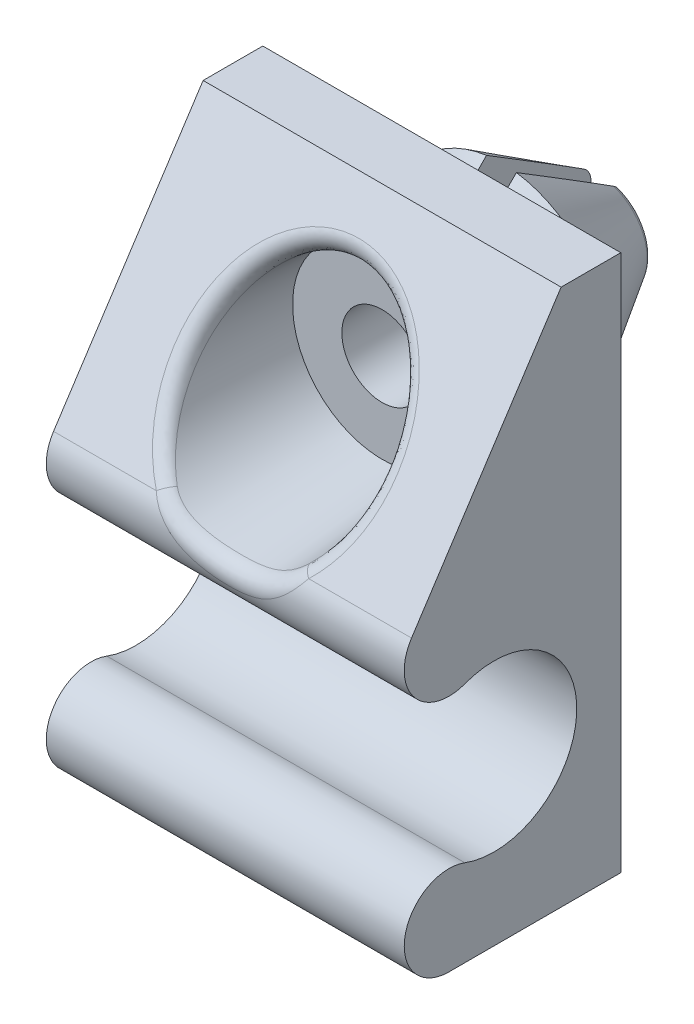
SolidWorks part; units mm, degrees
ref_plane "Front Plane" through (0, 0, 0) normal (0, 0, 1) x (1, 0, 0)
ref_plane "Top Plane" through (0, 0, 0) normal (0, 1, 0) x (1, 0, 0)
ref_plane "Right Plane" through (0, 0, 0) normal (1, 0, 0) x (0, 0, -1)
sketch "Sketch2" plane through (400, 0, -0.75) normal (1, 0, 0) x (0, 1, 0)
  line L0 (-13, 6.5085) -> (-13, 0.75)
  line L1 (-13, 0.75) -> (5, 0.75)
  line L2 (5, 0.75) -> (5, 2.75)
  line L3 (-7.5, 5) -> (-7.5, 0.75) construction
  line L4 (-38.1, 0.75) -> (38.1, 0.75) construction
  line L5 (5, 2.75) -> (-2.6799, 7.7645)
  circle A0 centre (-7.5, 5) radius 2.775
  circle A1 centre (-11.5, 6.5085) radius 1.5
  circle A2 centre (-7.5, 5) radius 2.525 construction
  circle A3 centre (-3.5, 6.5085) radius 1.5
  point P16 (-5, 6.5085)
  point P17 (-10, 6.5085)
  point P18 (-2.6592, 7.7507)
  point P20 (0, 0)
  dimension "D1" = 0.25
  dimension "D2" = 3
  dimension "D3" = 5
  dimension "D4" = 2
  dimension "D5" = 5
extrude "Boss-Extrude1" add sketch "Sketch2" along normal mid plane 12 contours A1 | L3 A0 A1 L0 L1 | A0 L3 L1 L2 L5 A3 | A3 region at (400, -10.846, 1.9103) region at (400, -11.5, 5.7585) region at (400, -1.0175, 2.191) region at (400, -3.5, 5.7585)
ref_plane "Plane1" through (400, 0, 0) normal (1, 0, 0) x (0, 0, -1)
sketch "Sketch4" plane through (400, 0, 0) normal (1, 0, 0) x (0, 0, -1)
  line L0 (0, -3.11) -> (1.5, -3.11)
  line L1 (0, -13) -> (0, 5) construction
  line L2 (1.5, -3.11) -> (2, -3.61)
  line L3 (2, -3.61) -> (5.2598, -1.6272)
  line L4 (5, -0.7) -> (2.5, -0.7)
  line L5 (2.5, -0.7) -> (0, -1.35)
  line L6 (0, 3.11) -> (0, -3.11) construction
  line L7 (0, 3.11) -> (0, -3.11)
  line L8 (1.5, -3.11) -> (1.5, 3.11) construction
  line L9 (1.5, -38.1) -> (1.5, 38.1) construction
  line L10 (0, 0) -> (5.8628, 0) construction
  arc A0 (5.2598, -1.6272) -> (5, -0.7) centre (5, -1.2) ccw
  point P10 (0, 0)
  point P16 (6.7842, -0.7)
  point P20 (5.2264, -1.5466)
  point P21 (0, 0)
  point P22 (0, 0)
  dimension "D3" = 0.5
  dimension "D1" = 1.35
  dimension "D2" = 5
  dimension "D4" = 0.7
  dimension "D5" = 2.5
  dimension "D6" = 0.5
  dimension "D7" = 0.5
revolve "Revolve1" add sketch "Sketch4" angle 360 about L10 region at (400, -1.8933, -2.4762)
sketch "Sketch5" plane through (0, 0, 0) normal (0, 0, -1) x (-1, 0, 0)
  line L0 (-400, 3.9922) -> (-400, -3.9922) construction
  line L1 (-399.5, -5) -> (-400.5, -5)
  line L2 (-399.5, -5) -> (-399.5, 5)
  line L3 (-399.5, 5) -> (-400.5, 5)
  line L4 (-400.5, -5) -> (-400.5, 5)
  line L5 (-399.5, -5) -> (-400.5, 5) construction
  line L6 (-399.5, 5) -> (-400.5, -5) construction
  line L7 (-406, 5) -> (-394, 5) construction
  point P0 (-400, 0)
  dimension "D1" = 1
extrude "Cut-Extrude1" cut sketch "Sketch5" along normal through all
ref_plane "Plane2" through (0, 0, 2) normal (0, 0, 1) x (1, 0, 0)
sketch "Sketch6" plane through (0, 0, 2) normal (0, 0, 1) x (1, 0, 0)
  circle A0 centre (400, 0) radius 3
  arc A1 (399.5, 3.0695) -> (399.5, -3.0695) centre (400, 0) ccw construction
  dimension "D1" = 6
extrude "Cut-Extrude2" cut sketch "Sketch6" along normal blind 10 draft 5 draft outward yes
fillet "Fillet1" radius 0.5 2 edges at (400.5847, -3.4101, 7.2558) (400, 3.1081, 3.2353)
sketch "Sketch7" plane through (0, 0, 2) normal (0, 0, 1) x (1, 0, 0)
  circle A0 centre (400, 0) radius 1.35
  arc A1 (399.5, 1.254) -> (399.5, -1.254) centre (400, 0) ccw construction
extrude "Cut-Extrude3" cut sketch "Sketch7" against normal up to surface (2 mm away) up to face at (401.365, 0, 0)
